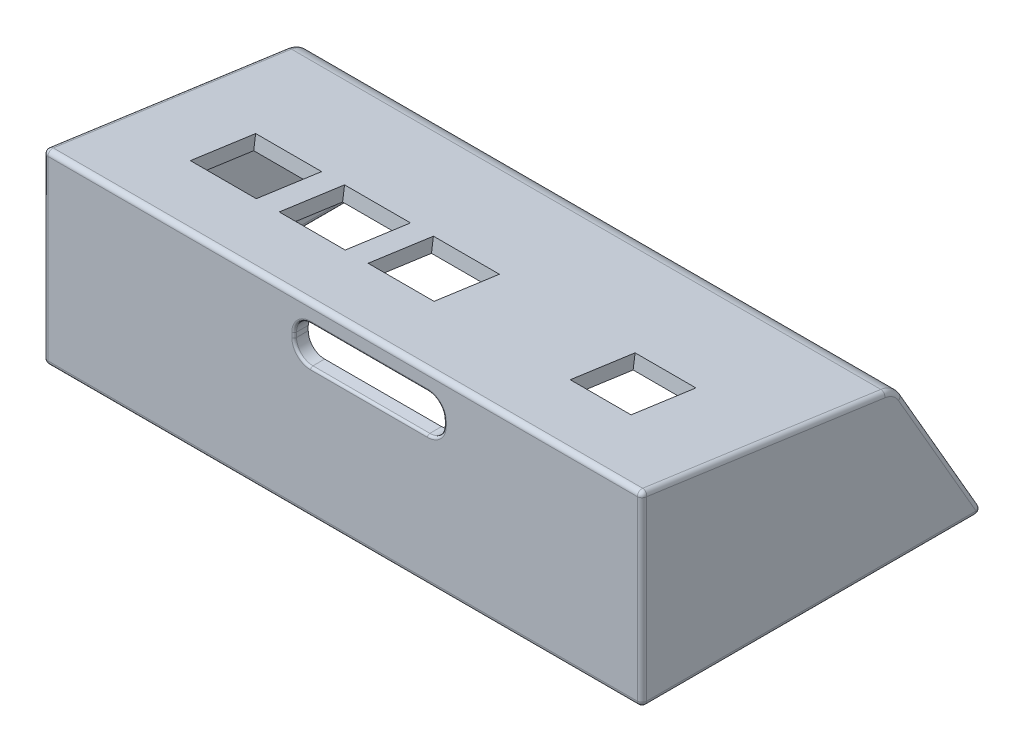
SolidWorks part; units mm, degrees
ref_plane "前视基准面" through (0, 0, 0) normal (0, 0, 1) x (1, 0, 0)
ref_plane "上视基准面" through (0, 0, 0) normal (0, 1, 0) x (1, 0, 0)
ref_plane "右视基准面" through (0, 0, 0) normal (1, 0, 0) x (0, 0, -1)
other "Configuration Table"
sketch "草图1" plane through (0, 0, 0) normal (1, 0, 0) x (0, 0, -1)
  line L0 (0, 0) -> (3, 0)
  line L1 (73.1394, 0) -> (54.4647, 32.3455)
  line L2 (54.4647, 32.3455) -> (0, 40)
  line L3 (0, 40) -> (0, 0)
  line L5 (69.6753, 0) -> (52.5983, 29.5783)
  line L6 (52.5983, 29.5783) -> (3, 36.5489)
  line L7 (3, 36.5489) -> (3, 0)
  line L8 (3, 36.5489) -> (3, 3) construction
  line L9 (67.9433, 3) -> (52.5983, 29.5783) construction
  line L10 (69.6753, 0) -> (73.1394, 0)
  line L11 (0, 0) -> (73.1394, 0) construction
  line L12 (3, 3) -> (67.9433, 3) construction
  dimension "D1" = 55
  dimension "D2" = 3
  dimension "D3" = 40
extrude "凸台-拉伸1" add sketch "草图1" along normal blind 125
sketch "草图2" plane through (0, 39.2252, -5.5127) normal (0, 0.9903, -0.1392) x (1, 0, 0)
  line L1 (97.149, 24.0931) -> (110.149, 24.0931)
  line L2 (97.149, 24.0931) -> (97.149, 10.0931)
  line L3 (97.149, 10.0931) -> (110.149, 10.0931)
  line L4 (110.149, 24.0931) -> (110.149, 10.0931)
  line L5 (53.988, 24.1431) -> (68.088, 24.1431)
  line L6 (53.988, 24.1431) -> (53.988, 10.0431)
  line L7 (53.988, 10.0431) -> (68.088, 10.0431)
  line L8 (68.088, 24.1431) -> (68.088, 10.0431)
  line L18 (62.5, 41.0069) -> (62.5, -31.3643) construction
  line L19 (125, 49.4331) -> (125, -5.5669) construction
  line L20 (34.988, 24.1431) -> (49.088, 24.1431)
  line L21 (34.988, 24.1431) -> (34.988, 10.0431)
  line L22 (34.988, 10.0431) -> (49.088, 10.0431)
  line L23 (49.088, 24.1431) -> (49.088, 10.0431)
  line L24 (15.988, 24.1431) -> (30.088, 24.1431)
  line L25 (15.988, 24.1431) -> (15.988, 10.0431)
  line L26 (15.988, 10.0431) -> (30.088, 10.0431)
  line L27 (30.088, 24.1431) -> (30.088, 10.0431)
  line L31 (-5.112, 17.0931) -> (145.7545, 17.0931) construction
  line L32 (125, -5.5669) -> (0, -5.5669) construction
  dimension "D1" = 13
  dimension "D2" = 14
  dimension "D3" = 14.1
  dimension "D4" = 14.1
  dimension "D5" = 7.05
  dimension "D7" = 62.5
  dimension "D8" = 7
  dimension "D9" = 34.649
  dimension "D10" = 3
  dimension "D6" = 8.512
  dimension "D11" = 22.66
extrude "切除-拉伸1" cut sketch "草图2" against normal blind 5
sketch "草图4" plane through (0, 0, 0) normal (0, 0, 1) x (1, 0, 0)
  line L0 (125, 40) -> (0, 40) construction
  line L1 (53.649, 35.9) -> (85.649, 35.9)
  line L2 (53.649, 35.9) -> (53.649, 27.9)
  line L3 (53.649, 27.9) -> (85.649, 27.9)
  line L4 (85.649, 35.9) -> (85.649, 27.9)
  line L5 (62.5, 49.94) -> (62.5, 4.3344) construction
  dimension "D1" = 4.1
  dimension "D2" = 23.149
  dimension "D3" = 8.851
  dimension "D4" = 8
extrude "切除-拉伸2" cut sketch "草图4" against normal blind 3
fillet "圆角2" radius 3.5 4 edges at (53.649, 27.9, -1.5) (53.649, 35.9, -1.5) (85.649, 27.9, -1.5) (85.649, 35.9, -1.5)
sketch "草图5" plane through (0, 0, 0) normal (-1, 0, 0) x (0, 0, 1)
  line L0 (-69.6753, 0) -> (-3, 0)
  line L8 (0, 0) -> (0, 40)
  line L9 (0, 40) -> (-54.4647, 32.3455)
  line L10 (-54.4647, 32.3455) -> (-73.1394, 0)
  line L11 (-73.1394, 0) -> (-69.6753, 0)
  line L12 (-69.6753, 0) -> (-52.5983, 29.5783)
  line L13 (-52.5983, 29.5783) -> (-3, 36.5489)
  line L14 (-3, 36.5489) -> (-3, 0)
  line L15 (-3, 0) -> (0, 0)
  line L16 (0, 0) -> (0, 40)
  line L17 (0, 40) -> (-54.4647, 32.3455)
  line L18 (-54.4647, 32.3455) -> (-73.1394, 0)
  line L19 (-73.1394, 0) -> (-69.6753, 0)
  line L23 (-3, 0) -> (0, 0)
  dimension "D1" = 0
extrude "凸台-拉伸2" add sketch "草图5" against normal blind 3
sketch "草图6" plane through (125, 0, 0) normal (1, 0, 0) x (0, 0, -1)
  line L0 (3, 0) -> (69.6753, 0)
  line L8 (0, 40) -> (0, 0)
  line L9 (0, 0) -> (3, 0)
  line L10 (3, 0) -> (3, 36.5489)
  line L11 (3, 36.5489) -> (52.5983, 29.5783)
  line L12 (52.5983, 29.5783) -> (69.6753, 0)
  line L13 (69.6753, 0) -> (73.1394, 0)
  line L14 (73.1394, 0) -> (54.4647, 32.3455)
  line L15 (54.4647, 32.3455) -> (0, 40)
  line L16 (0, 40) -> (0, 0)
  line L17 (0, 0) -> (3, 0)
  line L21 (69.6753, 0) -> (73.1394, 0)
  line L22 (73.1394, 0) -> (54.4647, 32.3455)
  line L23 (54.4647, 32.3455) -> (0, 40)
  dimension "D1" = 0
extrude "凸台-拉伸3" add sketch "草图6" along normal blind 3
fillet "圆角5" radius 5 1 edges at (64, 32.3455, -54.4647)
fillet "圆角6" radius 1 6 edges at (0, 31.8787, -54.1499) (128, 31.8787, -54.1499) (128, 36.3424, -26.0249) (0, 36.3424, -26.0249) (0, 15.1168, -64.4117) (128, 15.1168, -64.4117)
fillet "圆角8" radius 1 5 edges at (128, 0, -35.9924) (127.7071, 0, -72.8012) (0, 0, -35.9924) (0.2929, 0, -72.8012) (64, 0, -73.1394)
fillet "圆角9" radius 1 8 edges at (127.7071, 0.2929, 0) (128, 19.9951, 0) (127.7071, 39.7042, 0) (64, 40, 0) (0.2929, 39.7042, 0) (0, 19.9951, 0) (0.2929, 0.2929, 0) (64, 0, 0)
fillet "圆角10" radius 0.5 8 edges at (54.6741, 28.9251, 0) (53.649, 31.9, 0) (54.6741, 34.8749, 0) (69.649, 27.9, 0) (84.6239, 28.9251, 0) (85.649, 31.9, 0) (84.6239, 34.8749, 0) (69.649, 35.9, 0)
fillet "圆角11" radius 1 4 edges at (125, 0, -36.3377) (64, 0, -69.6753) (64, 0, -3) (3, 0, -36.3377)
